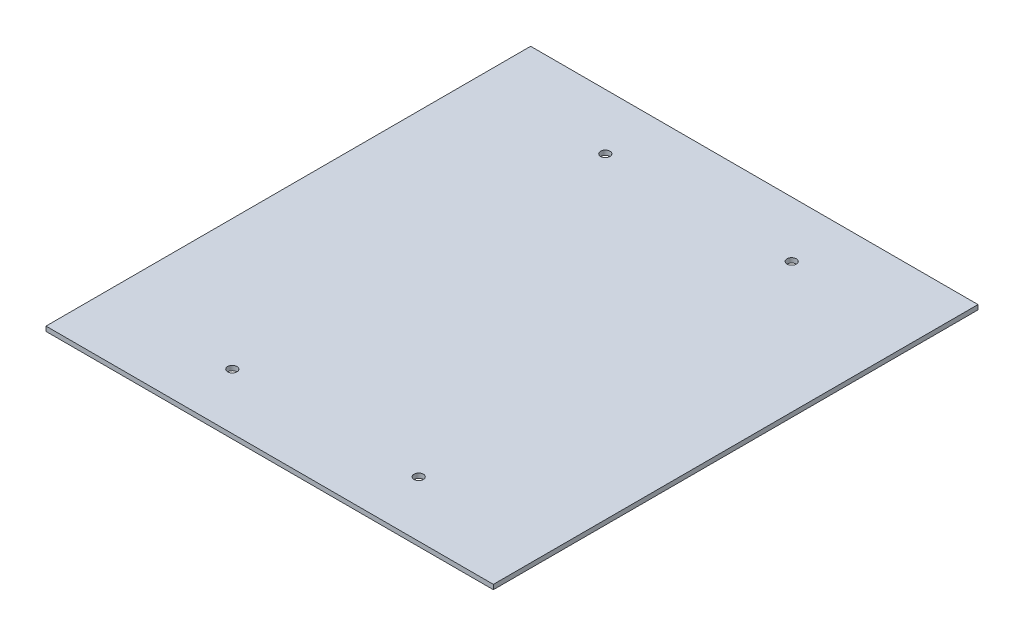
SolidWorks part; units mm, degrees
ref_plane "Front Plane" through (0, 0, 0) normal (0, 0, 1) x (1, 0, 0)
ref_plane "Top Plane" through (0, 0, 0) normal (0, 1, 0) x (1, 0, 0)
ref_plane "Right Plane" through (0, 0, 0) normal (1, 0, 0) x (0, 0, -1)
sketch "Sketch2" plane through (0, 0, 0) normal (0, 1, 0) x (1, 0, 0)
  line L1 (-152.4, -165.1) -> (152.4, -165.1)
  line L2 (-152.4, -165.1) -> (-152.4, 165.1)
  line L3 (-152.4, 165.1) -> (152.4, 165.1)
  line L4 (152.4, -165.1) -> (152.4, 165.1)
  line L5 (-152.4, -165.1) -> (152.4, 165.1) construction
  line L6 (-152.4, 165.1) -> (152.4, -165.1) construction
  point P0 (0, 0)
  dimension "D1" = 304.8
  dimension "D2" = 330.2
base flange "Base-Flange1" sketch "Sketch2" thickness 3.175 reverse thickness direction no parameters "D1"=0.7366
sketch "Sketch7" plane through (0, 0, 0) normal (0, 1, 0) x (1, 0, 0)
  line L1 (-63.5, -127.06) -> (63.5, -127.06) construction
  line L2 (-63.5, -127.06) -> (-63.5, 127.06) construction
  line L3 (-63.5, 127.06) -> (63.5, 127.06) construction
  line L4 (63.5, -127.06) -> (63.5, 127.06) construction
  line L5 (-63.5, -127.06) -> (63.5, 127.06) construction
  line L6 (-63.5, 127.06) -> (63.5, -127.06) construction
  circle A0 centre (-63.5, 127.06) radius 3.175
  circle A1 centre (63.5, 127.06) radius 3.175
  circle A2 centre (63.5, -127.06) radius 3.175
  circle A3 centre (-63.5, -127.06) radius 3.175
  point P0 (0, 0)
  dimension "D3" = 6.35
  dimension "D1" = 127
  dimension "D2" = 254.12
extrude "Cut-Extrude1" cut sketch "Sketch7" against normal through all normal cut yes
sketch "Bend-Lines1" [suppressed] plane through (0, 0, 0) normal (0, 1, 0) x (1, 0, 0)
sketch "Bounding-Box1" [suppressed] plane through (0, 0, 0) normal (0, 1, 0) x (1, 0, 0)
sheet metal parameters "Sheet-Metal1" thickness 3.175 parameters "D1"=0.7366
flat pattern "Flat-Pattern1" [suppressed]
sketch "Bend-Lines2" plane through (0, 0, 0) normal (0, 1, 0) x (1, 0, 0)
sketch3d "Bounding-Box2" [suppressed]
  line L0 (-165, -165, 0) -> (-165, 165, 0) construction
  line L1 (165, -165, 0) -> (165, 165, 0) construction
  line L2 (-165, -165, 0) -> (165, -165, 0) construction
  line L3 (-165, 165, 0) -> (165, 165, 0) construction
sheet metal parameters "Sheet-Metal2" thickness 3.175 parameters "D1"=0.7366
flat pattern "Flat-Pattern1"
sketch "Bend-Lines2" plane through (0, 0, 0) normal (0, 1, 0) x (1, 0, 0)
sketch3d "Bounding-Box2" [suppressed]
  line L0 (-152.4, -165.1, 0) -> (-152.4, 165.1, 0) construction
  line L1 (152.4, -165.1, 0) -> (152.4, 165.1, 0) construction
  line L2 (-152.4, -165.1, 0) -> (152.4, -165.1, 0) construction
  line L3 (-152.4, 165.1, 0) -> (152.4, 165.1, 0) construction
